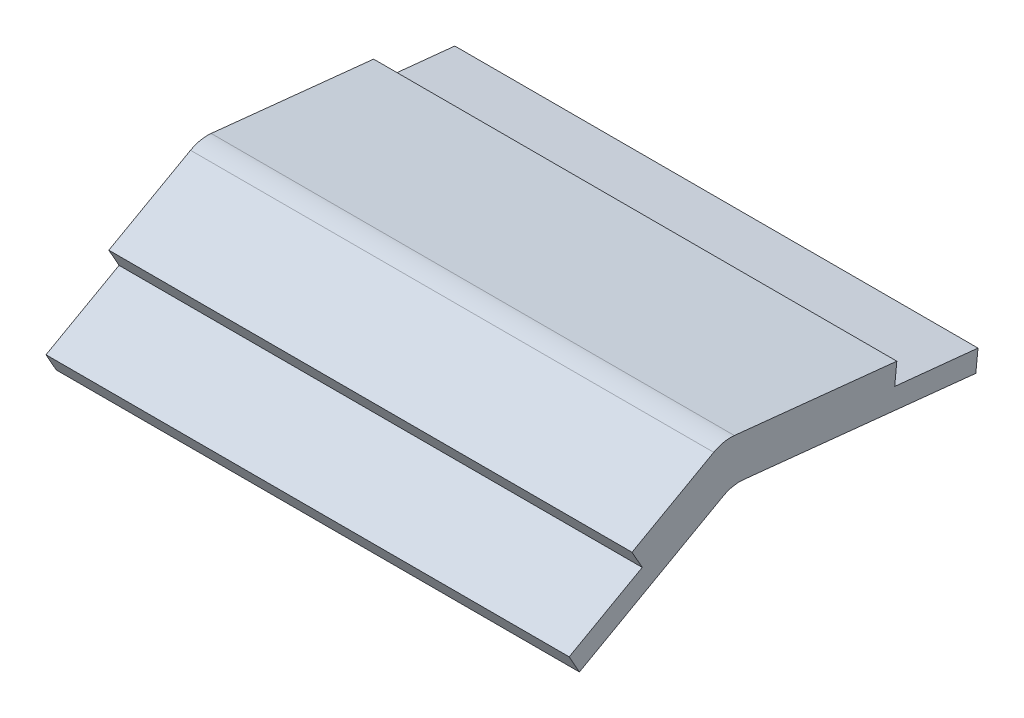
SolidWorks part; units mm, degrees
ref_plane "Front Plane" through (0, 0, 0) normal (0, 0, 1) x (1, 0, 0)
ref_plane "Top Plane" through (0, 0, 0) normal (0, 1, 0) x (1, 0, 0)
ref_plane "Right Plane" through (0, 0, 0) normal (1, 0, 0) x (0, 0, -1)
sketch "Sketch1" plane through (0, 0, 0) normal (1, 0, 0) x (0, 0, -1)
  line L6 (-17.0451, 11.0948) -> (-15.5805, 8.4766)
  line L7 (-17.0451, 11.0948) -> (-5.3363, 17.6448)
  line L8 (-2.3791, 18.2544) -> (20.9122, 15.8371)
  line L9 (20.9122, 15.8371) -> (20.6102, 12.8523)
  line L12 (-3.9542, 18.4179) -> (0, 0) construction
  line L13 (-15.5805, 8.4766) -> (-26.0533, 2.6182)
  line L14 (-26.0533, 2.6182) -> (-24.5887, 0)
  line L15 (-24.5887, 0) -> (-4.0185, 11.5069)
  line L16 (-1.0613, 12.1166) -> (32.2396, 8.6604)
  line L18 (20.6102, 12.8523) -> (32.5493, 11.6444)
  line L19 (32.5493, 11.6444) -> (32.2396, 8.6604)
  line L20 (0, 0) -> (50000, 0) construction
  arc A0 (-2.3791, 18.2544) -> (-5.3363, 17.6448) centre (-2.8952, 13.2811) ccw
  arc A1 (-1.0613, 12.1166) -> (-4.0185, 11.5069) centre (-1.5775, 7.1433) ccw
  point P23 (-2.6365, 12.2801)
  dimension "D12" = 5
  dimension "D13" = 5
  dimension "D1" = 25
  dimension "D2" = 15
  dimension "D3" = 145
  dimension "D5" = 12
  dimension "D6" = 12
  dimension "D7" = 3
  dimension "D8" = 3
  dimension "D9" = 3
  dimension "D10" = 3
extrude "Boss-Extrude1" add sketch "Sketch1" along normal blind 75
sketch "Sketch3" plane through (0, 11.8785, -1.2328) normal (0, -0.9947, 0.1032) x (1, 0, 0)
  line L0 (75, 2.3065) -> (0, 2.3065) construction
  line L1 (0, -31.1733) -> (3, -31.1733)
  line L2 (0, -31.1733) -> (0, 2.3065)
  line L3 (0, 2.3065) -> (3, 2.3065)
  line L4 (3, -31.1733) -> (3, 2.3065)
  dimension "D1" = 3
extrude "Boss-Extrude2" add sketch "Sketch3" along normal blind 8
